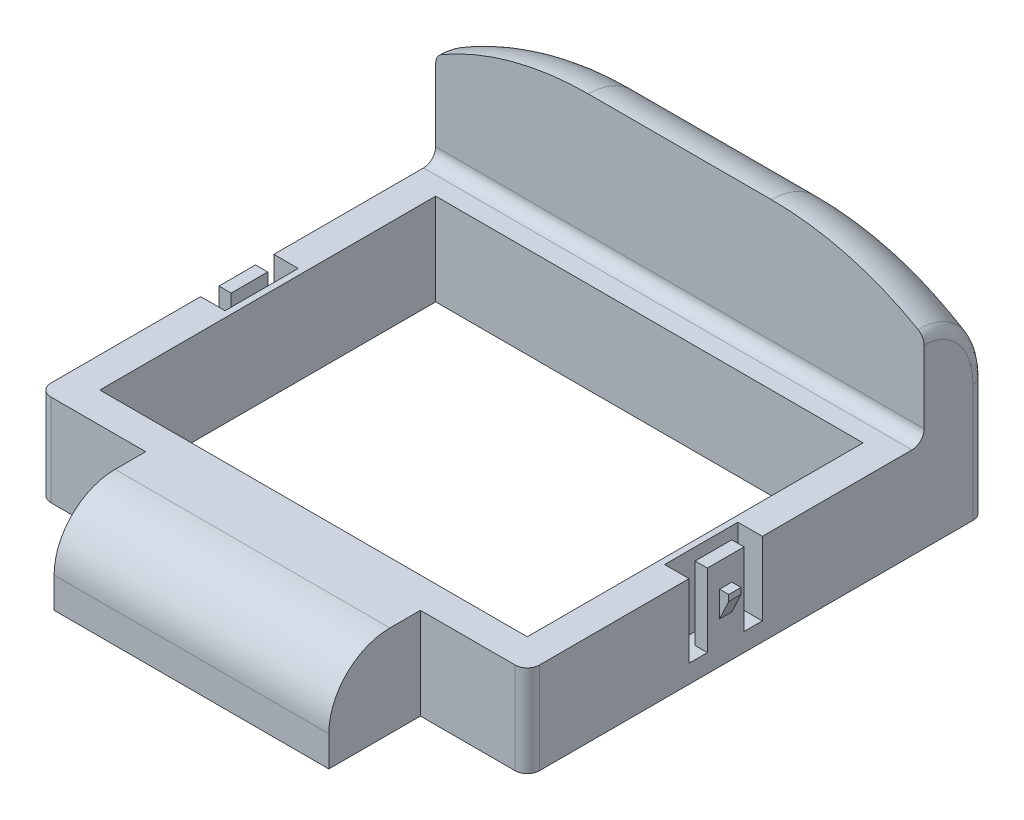
SolidWorks part; units mm, degrees
note: '?' marks a value the reader was unsure of.
ref_plane "Спереди" through (0, 0, 0) normal (0, 0, 1) x (1, 0, 0)
ref_plane "Сверху" through (0, 0, 0) normal (0, 1, 0) x (1, 0, 0)
ref_plane "Справа" through (0, 0, 0) normal (1, 0, 0) x (0, 0, -1)
sketch "Эскиз1" plane through (0, 0, 0) normal (0, 1, 0) x (1, 0, 0)
  line L0 (0, 0) -> (0, 54.6687) construction
  line L1 (40, 36.5) -> (-40, 36.5)
  line L2 (40, 36.5) -> (40, -36.5)
  line L3 (38, -38.5) -> (-38, -38.5)
  line L4 (-40, 36.5) -> (-40, -36.5)
  line L5 (-35, 21.5) -> (35, 21.5)
  line L6 (-35, 21.5) -> (-35, -33.5)
  line L7 (-35, -33.5) -> (35, -33.5)
  line L8 (35, 21.5) -> (35, -33.5)
  line L9 (22.5, -38.5) -> (-22.5, -38.5)
  line L10 (22.5, -38.5) -> (22.5, -53.5)
  line L11 (22.5, -53.5) -> (-22.5, -53.5)
  line L12 (-22.5, -38.5) -> (-22.5, -53.5)
  line L13 (0, 0) -> (50000, 0) construction
  arc A0 (-40, -36.5) -> (-38, -38.5) centre (-38, -36.5) ccw
  arc A1 (38, -38.5) -> (40, -36.5) centre (38, -36.5) ccw
  point P0 (0, 0)
  point P12 (0, 36.5)
  point P13 (0, 21.5)
  point P14 (0, -53.5)
  point P18 (40, 0)
  point P20 (-6.6161, 37.5)
  point P30 (0, 0)
  dimension "D10" = 2
  dimension "D1" = 80
  dimension "D2" = 70
  dimension "D3" = 15
  dimension "D4" = 75
  dimension "D5" = 55
  dimension "D6" = 5
  dimension "D7" = 20
  dimension "D8" = 45
  dimension "D9" = 15
extrude "Бобышка-Вытянуть2" add sketch "Эскиз1" along normal blind 15 contours L8 L5 L6 L7 | L3 L12 L11 L10
fillet "Скругление1" radius 10 1 edges at (0, 15, 53.5)
sketch "Эскиз3" plane through (0, 0, -36.5) normal (0, 0, -1) x (-1, 0, 0)
  line L0 (40, 15) -> (40, 0) construction
  line L1 (-40, 0) -> (40, 0)
  line L2 (-40, 0) -> (-40, 30)
  line L3 (-40, 30) -> (40, 30)
  line L4 (40, 0) -> (40, 30)
  line L6 (-15, 37) -> (15, 37)
  arc A0 (-40, 30) -> (-15, 37) centre (-15, -11.1429) cw
  arc A1 (15, 37) -> (40, 30) centre (15, -11.1429) cw
  point P7 (0, 37)
  point P10 (0, 30)
  dimension "D2" = 7
  dimension "D1" = 30
  dimension "D3" = 30
extrude "Бобышка-Вытянуть4" add sketch "Эскиз3" against normal blind 10
fillet "Скругление6" radius 10 3 edges at (0, 37, -36.5) (-27.9808, 35.217, -36.5) (27.9808, 35.217, -36.5) tangent propagation no
fillet "Скругление7" radius 2 4 edges at (-40, 8.8324, -36.5) (40, 8.8324, -36.5) (-40, 28.0338, -32.0313) (40, 26.1885, -33.8448)
sketch "Эскиз4" plane through (0, 0, 0) normal (0, -1, 0) x (1, 0, 0)
  line L0 (38, -36.5) -> (-38, -36.5) construction
  line L1 (-40, -34.5) -> (-40, 36.5) construction
  circle A0 centre (-37, -30.5) radius 1
  dimension "D1" = 6
  dimension "D3" = 2
  dimension "D2" = 3
extrude "Вырез-Вытянуть1" cut sketch "Эскиз4" against normal blind 5 contours A0
fillet "Скругление8" radius 0.5 1 edges at (-37, 0, -31.5)
mirror "Зеркальное отражение3" about plane through (0, 0, 0) normal (1, 0, 0) of "Вырез-Вытянуть1", "Скругление8"
sketch "Эскиз7" plane through (0, 15, 0) normal (0, 1, 0) x (1, 0, 0)
  line L0 (-40, 0) -> (-36, 0)
  line L1 (-40, 26.5) -> (-40, -36.5) construction
  line L2 (-36, 0) -> (-36, -12)
  line L3 (-36, -12) -> (-40, -12)
  line L4 (-40, -12) -> (-40, -9)
  line L5 (-40, -9) -> (-38, -9)
  line L6 (-38, -9) -> (-38, -3)
  line L7 (-38, -3) -> (-40, -3)
  line L8 (-40, -3) -> (-40, 0)
  line L9 (-22.5, -38.5) -> (-38, -38.5) construction
  line L10 (-50, 0) -> (50, 0) construction
  point P12 (-38, -6)
  point P13 (-38, -12)
  point P14 (-40, -10.5)
  point P15 (-36, -6)
  dimension "D1" = 32.5
  dimension "D2" = 12
  dimension "D3" = 6
  dimension "D4" = 4
  dimension "D5" = 2
extrude "Вырез-Вытянуть3" cut sketch "Эскиз7" against normal blind 12 contours L3 L4 L5 L6 L7 L8 L0 L2
ref_plane "Плоскость3" through (0, 0, 6) normal (0, 0, 1) x (1, 0, 0)
sketch "Эскиз8" plane through (0, 0, 6) normal (0, 0, 1) x (1, 0, 0)
  line L0 (-40, 11) -> (-41.5, 11)
  line L1 (-41.5, 11) -> (-41.5, 10)
  line L2 (-41.5, 10) -> (-40, 6.7832)
  line L3 (-40, 6.7832) -> (-40, 11)
  line L4 (-40, 3) -> (-40, 15) construction
  line L5 (-22.5, 0) -> (-38, 0) construction
  dimension "D1" = 1.5
  dimension "D2" = 11
  dimension "D3" = 25
  dimension "D4" = 1
extrude "Бобышка-Вытянуть6" add sketch "Эскиз8" along normal mid plane 2
mirror "Зеркальное отражение5" about plane through (0, 0, 0) normal (1, 0, 0) of "Бобышка-Вытянуть6", "Вырез-Вытянуть3"
sketch "Эскиз5" plane through (-40, 0, 0) normal (-1, 0, 0) x (0, 0, 1)
  line L0 (-26.5, 15) -> (0, 15) construction
  line L1 (-4, 15) -> (16, 15)
  line L2 (-4, 15) -> (-4, 3)
  line L3 (-4, 3) -> (16, 3)
  line L4 (16, 15) -> (16, 3)
  line L5 (38.5, 15) -> (38.5, 0) construction
  point P6 (6, 3)
  dimension "D1" = 32.5
  dimension "D2" = 20
  dimension "D3" = 12
extrude "Вырез-Вытянуть2" [suppressed] cut sketch "Эскиз5" against normal blind 4
ref_plane "Плоскость2" [suppressed] through (0, 0, 6) normal (0, 0, 1) x (1, 0, 0)
ref_axis "Ось1" [suppressed] through (80.9, 3, 6) along (-1, 0, 0)?
sketch "Эскиз6" [suppressed] plane through (0, 0, 6) normal (0, 0, 1) x (1, 0, 0)
  line L0 (-38, 3) -> (-38, 15)
  line L1 (-38, 15) -> (-40, 15)
  line L2 (-41, 11) -> (-41, 9)
  line L3 (50, 0) -> (-50, 0) construction
  line L4 (-40, 7) -> (-40, 3)
  line L5 (-40, 3) -> (-38, 3)
  line L6 (-41, 9) -> (-40, 7)
  line L8 (-40, 15) -> (-40, 0) construction
  line L9 (-40, 15) -> (40, 15) construction
  line L11 (80.9, 3) -> (-80.9, 3) construction
  line L12 (-41, 11) -> (-40, 11)
  line L13 (-40, 11) -> (-40, 15)
  point P2 (-41, 15)
  point P4 (-40, 10.2395)
  point P5 (-40, 11.6734)
  point P12 (0, 0)
  point P14 (0, 0)
  point P16 (0, 0)
  point P17 (0, 0)
  point P18 (-39.9776, -0.045)
  point P19 (-39.7091, 0.4562)
  point P20 (-41, 15)
  point P21 (0, 0)
  point P22 (0, 0)
  point P23 (-41, 15)
  point P24 (0, 0)
  point P25 (0, 0)
  point P27 (0, 0)
  point P28 (-40.3179, 15)
  point P29 (-40.1312, 15)
  point P30 (0, 0)
  point P33 (0, 0)
  dimension "D1" = 2
  dimension "D2" = 3
  dimension "D3" = 11
  dimension "D4" = 2
  dimension "D5" = 2
extrude "Бобышка-Вытянуть5" [suppressed] add sketch "Эскиз6" along normal mid plane 8
mirror "Зеркальное отражение4" [suppressed] about plane through (0, 0, 0) normal (1, 0, 0)
fillet "Скругление9" radius 2 1 edges at (0, 15, -26.5)
